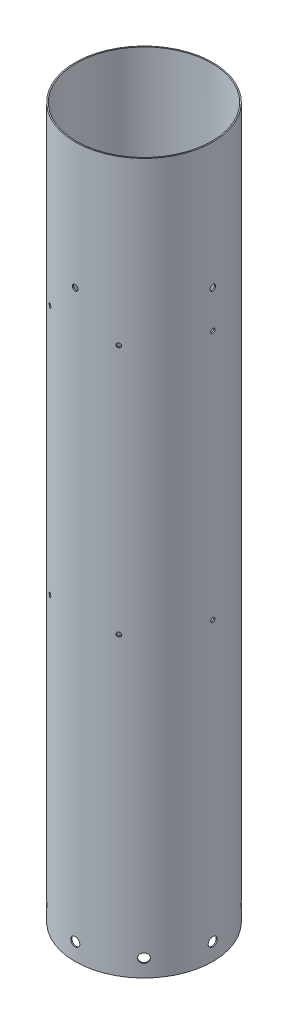
SolidWorks part; units mm, degrees
material "A-Glass Fiber"
ref_plane "Front Plane" through (0, 0, 0) normal (0, 0, 1) x (1, 0, 0)
ref_plane "Top Plane" through (0, 0, 0) normal (0, 1, 0) x (1, 0, 0)
ref_plane "Right Plane" through (0, 0, 0) normal (1, 0, 0) x (0, 0, -1)
sketch "Sketch2" plane through (0, 0, 0) normal (0, 1, 0) x (1, 0, 0)
  circle A0 centre (0, 0) radius 74.93
  circle A1 centre (0, 0) radius 76.2
  dimension "D1" = 152.4
  dimension "D2" = 1.27
extrude "Boss-Extrude1" add sketch "Sketch2" along normal blind 785.495
sketch "Sketch3" plane through (0, 127, 0) normal (1, 0, 0) x (0, 0, -1)
  circle A0 centre (0, -44.45) radius 4.7625 construction
  circle A1 centre (0, -44.45) radius 4.7625 construction
  circle A2 centre (0, -44.45) radius 5.0165
  dimension "D1" = 0.254
extrude "LOX to Kero, LOX Side Holes" [suppressed] cut sketch "Sketch3" along normal up to surface (76.0347 mm away) up to face at (0, 785.495, 76.2)
pattern_circular "CirPattern1" [suppressed] count 8 over 360 of bodies 102
sketch "Sketch4" plane through (0, -25.4, 0) normal (1, 0, 0) x (0, 0, 1)
  circle A0 centre (0, -44.45) radius 4.7625 construction
  circle A1 centre (0, -44.45) radius 4.7625 construction
  circle A2 centre (0, -44.45) radius 5.0165
  dimension "D1" = 0.254
extrude "LOX to Kero, Kero Side Holes" [suppressed] cut sketch "Sketch4" along normal up to surface (76.0347 mm away) up to face at (0, 785.495, 76.2)
pattern_circular "CirPattern2" [suppressed] count 8 over 360 of bodies 104
sketch "Sketch5" plane through (0, -25.4, 0) normal (1, 0, 0) x (0, 0, 1)
  circle A0 centre (0, -44.45) radius 4.7625 construction
  circle A1 centre (0, -44.45) radius 4.7625 construction
  circle A2 centre (0, -44.45) radius 5.0165
  dimension "D1" = 0.254
extrude "N2 to LOX, LOX Side Holes" cut sketch "Sketch5" along normal up to surface (76.0347 mm away) up to face at (0, 785.495, 76.2)
pattern_circular "CirPattern3" count 8 over 360 about axis through (0, 0, 0) along (0, 1, 0) of "N2 to LOX, LOX Side Holes" reverse direction yes
sketch "Sketch7" plane through (0, 0, 0) normal (1, 0, 0) x (0, 0, -1)
  line L0 (-2.3812, 327.3303) -> (2.3812, 327.3303) construction
  line L1 (0, 329.7115) -> (0, 324.949) construction
  line L2 (-2.3812, 604.52) -> (2.3812, 604.52) construction
  line L4 (0, 606.9012) -> (0, 602.1388) construction
  circle A0 centre (0, 604.52) radius 2.3812
  circle A2 centre (0, 327.3303) radius 2.3785
  spline S1 degree 3 poles (-2.3812, 327.3303) (-2.3812, 326.701) (-2.123, 326.0856) (-1.2443, 325.207) (-0.6225, 324.9494) (0.62, 324.9487) (1.2382, 325.2013) (2.1277, 326.0899) (2.381, 326.7078) (2.3815, 327.9511) (2.1241, 328.5729) (1.2467, 329.452) (0.6306, 329.7109) (-0.6258, 329.7122) (-1.2425, 329.4547) (-2.1225, 328.5761) (-2.3813, 327.9596) (-2.3812, 327.3303) (-2.3812, 326.701) (-2.123, 326.0856) knots -0.125 0 0 0 0.125 0.125 0.25 0.25 0.375 0.375 0.5 0.5 0.625 0.625 0.75 0.75 0.875 0.875 1 1 1 1.125 1.125 1.25 only from (-2.3812, 327.3303) to (-2.3812, 327.3303) construction
  spline S2 degree 3 poles (-2.3812, 327.3303) (-2.3812, 326.701) (-2.123, 326.0856) (-1.2443, 325.207) (-0.6225, 324.9494) (0.62, 324.9487) (1.2382, 325.2013) (2.1277, 326.0899) (2.381, 326.7078) (2.3815, 327.9511) (2.1241, 328.5729) (1.2467, 329.452) (0.6306, 329.7109) (-0.6258, 329.7122) (-1.2425, 329.4547) (-2.1225, 328.5761) (-2.3813, 327.9596) (-2.3812, 327.3303) (-2.3812, 326.701) (-2.123, 326.0856) knots -0.125 0 0 0 0.125 0.125 0.25 0.25 0.375 0.375 0.5 0.5 0.625 0.625 0.75 0.75 0.875 0.875 1 1 1 1.125 1.125 1.25 only from (-2.3812, 327.3303) to (-2.3812, 327.3303) construction
  spline S3 degree 3 poles (-2.3812, 604.52) (-2.3812, 603.8907) (-2.123, 603.2754) (-1.2443, 602.3967) (-0.6225, 602.1391) (0.62, 602.1384) (1.2382, 602.391) (2.1277, 603.2797) (2.381, 603.8975) (2.3815, 605.1408) (2.1241, 605.7626) (1.2467, 606.6417) (0.6306, 606.9006) (-0.6258, 606.9019) (-1.2425, 606.6444) (-2.1225, 605.7658) (-2.3813, 605.1493) (-2.3812, 604.52) (-2.3812, 603.8907) (-2.123, 603.2754) knots -0.125 0 0 0 0.125 0.125 0.25 0.25 0.375 0.375 0.5 0.5 0.625 0.625 0.75 0.75 0.875 0.875 1 1 1 1.125 1.125 1.25 only from (-2.3812, 604.52) to (-2.3812, 604.52) construction
  point P8 (0, 327.3303)
  point P17 (0, 604.52)
extrude "Cut-Extrude2" cut sketch "Sketch7" against normal through all both and the other way through all
pattern_circular "CirPattern4" count 4 over 180 about axis through (0, 785.495, 0) along (0, -1, 0) of "Cut-Extrude2"
sketch "Sketch9" plane through (0, 0, 0) normal (1, 0, 0) x (0, 0, -1)
  line L0 (0, 785.495) -> (0, 633.095) construction
  line L1 (74.93, 785.495) -> (-74.93, 785.495) construction
  circle A0 centre (0, 645.795) radius 3.175
  dimension "D3" = 6.35
  dimension "D1" = 152.4
  dimension "D2" = 12.7
extrude "Cut-Extrude3" cut sketch "Sketch9" against normal through all both and the other way through all contours A0
pattern_circular "CirPattern5" count 3 over 180 about axis through (0, 785.495, 0) along (0, -1, 0) of "Cut-Extrude3"
